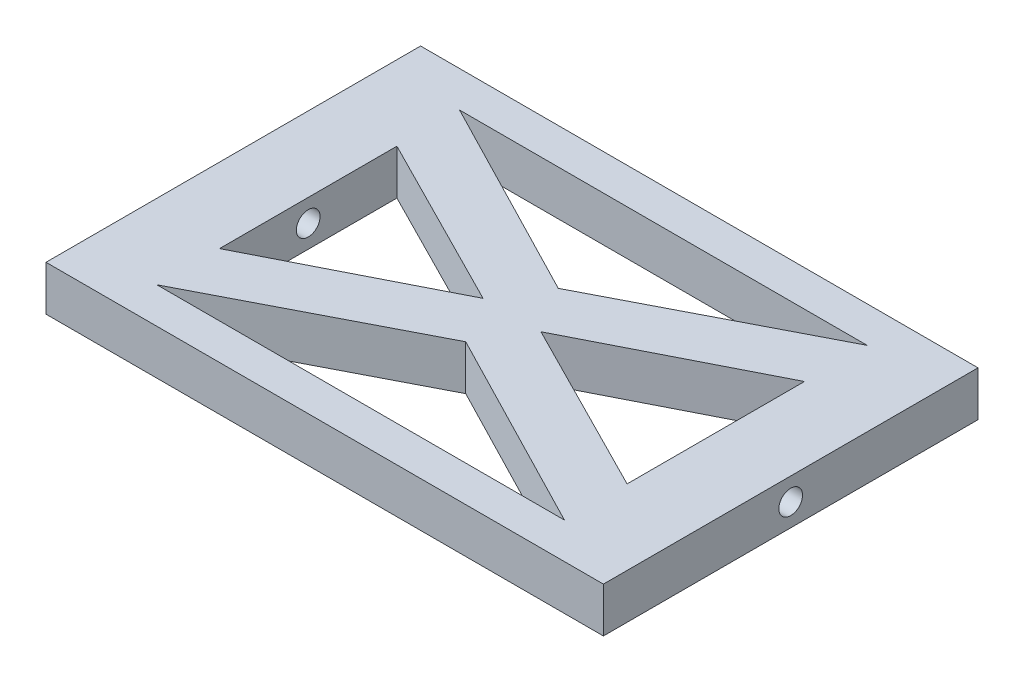
SolidWorks part; units mm, degrees
material "PLA"
ref_plane "Front" through (0, 0, 0) normal (0, 0, 1) x (1, 0, 0)
ref_plane "Top" through (0, 0, 0) normal (0, 1, 0) x (1, 0, 0)
ref_plane "Right" through (0, 0, 0) normal (1, 0, 0) x (0, 0, -1)
sketch "Sketch1" plane through (0, 0, 0) normal (0, 1, 0) x (1, 0, 0)
  line L1 (23.622, -15.875) -> (-23.622, -15.875)
  line L2 (23.622, -15.875) -> (23.622, 15.875)
  line L3 (23.622, 15.875) -> (-23.622, 15.875)
  line L4 (-23.622, -15.875) -> (-23.622, 15.875)
  line L5 (23.622, -15.875) -> (-23.622, 15.875) construction
  line L6 (23.622, 15.875) -> (-23.622, -15.875) construction
  point P0 (0, 0)
  dimension "D1" = 31.75
  dimension "D2" = 47.244
extrude "Boss-Extrude1" add sketch "Sketch1" along normal blind 3.81
sketch "Sketch2" plane through (0, 3.81, 0) normal (0, 1, 0) x (1, 0, 0)
  line L0 (-17.272, 3.175) -> (-17.272, 13.335)
  line L1 (-17.272, 13.335) -> (18.264, 13.335)
  line L2 (18.264, 13.335) -> (-17.272, 3.175)
  line L3 (23.622, 15.875) -> (-23.622, 15.875) construction
  line L4 (-23.622, 15.875) -> (-23.622, -15.875) construction
  line L5 (-17.272, -3.175) -> (-17.272, -13.335)
  line L6 (-17.272, -13.335) -> (18.264, -13.335)
  line L7 (18.264, -13.335) -> (-17.272, -3.175)
  line L8 (-23.622, -15.875) -> (23.622, -15.875) construction
  line L9 (-18.288, 13.335) -> (17.272, 13.335)
  line L10 (17.272, 13.335) -> (17.272, 3.175)
  line L11 (17.272, 3.175) -> (-18.288, 13.335)
  line L12 (23.622, -15.875) -> (23.622, 15.875) construction
  line L13 (17.272, -3.175) -> (17.272, -13.335)
  line L14 (17.272, -13.335) -> (-18.288, -13.335)
  line L15 (-18.288, -13.335) -> (17.272, -3.175)
  dimension "D1" = 10.16
  dimension "D2" = 2.54
  dimension "D3" = 6.35
  dimension "D4" = 35.536
  dimension "D5" = 35.536
  dimension "D6" = 2.54
  dimension "D7" = 10.16
  dimension "D8" = 35.56
  dimension "D9" = 6.35
  dimension "D10" = 10.16
  dimension "D11" = 35.56
  dimension "D12" = 10.16
sketch "Sketch4" plane through (23.622, 0, 0) normal (1, 0, 0) x (0, 0, -1)
  line L0 (0, 2.0955) -> (0, -2.0955) construction
  line L1 (17.4625, 0) -> (-17.4625, 0) construction
  circle A0 centre (0, 1.905) radius 1.0033
  dimension "D1" = 2.0066
  dimension "D2" = 1.905
extrude "Cut-Extrude3" cut sketch "Sketch4" against normal blind 7.62
sketch "Sketch5" plane through (-23.622, 0, 0) normal (-1, 0, 0) x (0, 0, 1)
  line L0 (0, -2.0955) -> (0, 2.0955) construction
  line L1 (17.4625, 0) -> (-17.4625, 0) construction
  circle A0 centre (0, 1.905) radius 1.0033
  dimension "D1" = 2.0066
  dimension "D2" = 1.905
extrude "Cut-Extrude4" cut sketch "Sketch5" against normal blind 7.62
sketch "Sketch6" plane through (0, 3.81, 0) normal (0, 1, 0) x (1, 0, 0)
  line L0 (0, 0) -> (-23.622, 0)
  line L1 (-23.622, 15.875) -> (-23.622, -15.875) construction
  line L2 (-23.622, 0) -> (23.622, 0)
  line L3 (23.622, -15.875) -> (23.622, 15.875) construction
  line L4 (0, 0) -> (0, 15.875)
  line L5 (23.622, 15.875) -> (-23.622, 15.875) construction
  line L6 (0, 15.875) -> (0, -15.875)
  line L7 (-23.622, -15.875) -> (23.622, -15.875) construction
  line L8 (0, 15.875) -> (0, 12.827)
  line L9 (-23.622, 12.827) -> (-17.272, 12.827)
  line L10 (-17.272, 12.827) -> (17.272, 12.827)
  line L11 (-17.272, 12.827) -> (0, 3.9214)
  line L12 (0, 3.9214) -> (0, 12.827)
  line L13 (17.272, 12.827) -> (0, 3.9214)
  line L14 (17.272, -12.827) -> (0, -3.9214)
  line L15 (-17.272, -12.827) -> (17.272, -12.827)
  line L16 (-17.272, -12.827) -> (0, -3.9214)
  line L17 (-17.272, -7.5168) -> (-17.272, 7.5168)
  line L18 (-17.272, 7.5168) -> (-2.4527, 0)
  line L19 (-2.4527, 0) -> (-9.8623, 3.7584)
  line L20 (-9.8623, 3.7584) -> (-7.7524, 7.9186)
  line L21 (-17.272, -7.5168) -> (-2.4527, 0)
  line L22 (17.272, 7.5168) -> (2.4527, 0)
  line L23 (17.272, -7.5168) -> (17.272, 7.5168)
  line L24 (17.272, -7.5168) -> (2.4527, 0)
  point P24 (-9.8623, 3.7584)
  point P29 (-17.272, 0)
  dimension "D1" = 6.35
  dimension "D2" = 3.048
extrude "Cut-Extrude6" cut sketch "Sketch6" against normal through all contours L24 L23 L2 | L2 L23 L22 | L13 L10 L6 | L10 L11 L6 | L18 L17 L2 | L17 L21 L2 | L16 L15 L6 | L6 L15 L14 region at (12.3322, 3.81, -2.5056) region at (12.3322, 3.81, 2.5056) region at (5.7573, 3.81, 9.8585) region at (-5.7573, 3.81, 9.8585) region at (-12.3322, 3.81, 2.5056) region at (-12.3322, 3.81, -2.5056) region at (-5.7573, 3.81, -9.8585) region at (5.7573, 3.81, -9.8585)
